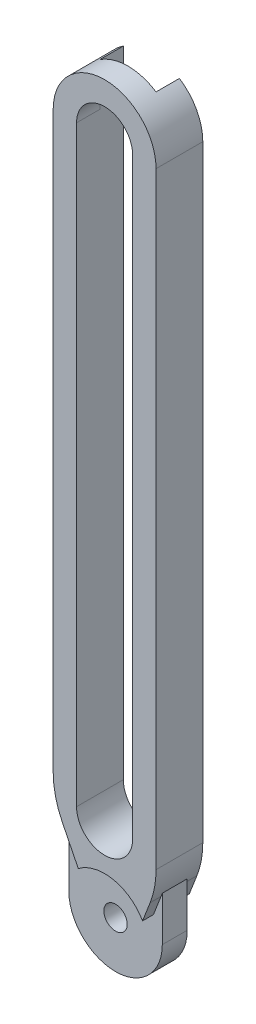
SolidWorks part; units mm, degrees
ref_plane "Piano frontale" through (0, 0, 0) normal (0, 0, 1) x (1, 0, 0)
ref_plane "Piano superiore" through (0, 0, 0) normal (0, 1, 0) x (1, 0, 0)
ref_plane "Piano destro" through (0, 0, 0) normal (1, 0, 0) x (0, 0, -1)
sketch "Schizzo1" plane through (0, 0, 0) normal (0, 0, 1) x (1, 0, 0)
  line L0 (0, -86.6264) -> (0, 113.3736) construction
  line L1 (-16.5, -86.6264) -> (-16.5, 113.3736)
  line L2 (16.5, -86.6264) -> (16.5, 113.3736)
  arc A0 (-16.5, -86.6264) -> (16.5, -86.6264) centre (0, -86.6264) ccw
  arc A1 (16.5, 113.3736) -> (-16.5, 113.3736) centre (0, 113.3736) ccw
  point P2 (0, 13.3736)
  dimension "D1" = 33
  dimension "D2" = 200
extrude "Estrusione-Estrusione1" add sketch "Schizzo1" along normal mid plane 15
sketch "Schizzo2" plane through (0, 0, 0) normal (0, 0, 1) x (1, 0, 0)
  line L0 (0, -88.7045) -> (0, -104.7045) construction
  line L1 (15, -88.7045) -> (15, -104.7045)
  line L2 (-15, -88.7045) -> (-15, -104.7045)
  line L3 (16.5, -86.6264) -> (-16.5, -86.6264) construction
  arc A0 (15, -88.7045) -> (-15, -88.7045) centre (0, -88.7045) ccw
  arc A1 (-15, -104.7045) -> (15, -104.7045) centre (0, -104.7045) ccw
  point P3 (0, -96.7045)
  dimension "D1" = 15
  dimension "D2" = 16
extrude "Estrusione-Estrusione2" add sketch "Schizzo2" along normal mid plane 8
sketch "Schizzo3" plane through (0, 0, 4) normal (0, 0, 1) x (1, 0, 0)
  line L0 (0, -104.7045) -> (15, -104.7045) construction
  line L1 (-8.4489, -93.5413) -> (-16.5, -77.3405)
  line L2 (-16.5, 113.3736) -> (-16.5, -86.6264) construction
  line L3 (-16.5, -77.3405) -> (-21.7067, -99.1177)
  line L4 (-21.7067, -99.1177) -> (-12.1597, -111.6429)
  line L5 (12.1644, -97.7744) -> (16.5, -86.6264)
  line L6 (16.5, -86.6264) -> (21.2626, -91.5332)
  line L7 (21.2626, -91.5332) -> (13.9976, -104.4458)
  arc A0 (-12.1597, -111.6429) -> (13.9976, -104.4458) centre (0, -104.7045) ccw
  arc A1 (12.1644, -97.7744) -> (-8.4489, -93.5413) centre (0, -104.7045) ccw
  arc A2 (-15, -93.5003) -> (15, -93.5003) centre (0, -86.6264) ccw construction
  dimension "D1" = 28
extrude "Taglio-Estrusione1" cut sketch "Schizzo3" along normal blind 4
mirror "Specchia1" about plane through (0, 0, 0) normal (0, 0, 1) of "Taglio-Estrusione1"
sketch "Schizzo4" plane through (0, 0, 4) normal (0, 0, 1) x (1, 0, 0)
  line L0 (-15, -93.5003) -> (-15, -80.3588)
  line L1 (-8.4489, -93.5413) -> (-16.5, -77.3405) construction
  line L2 (-15, -80.3588) -> (-16.5, -77.3405)
  line L3 (-16.5, -77.3405) -> (-16.5, -93.5003)
  line L4 (-16.5, -93.5003) -> (-15, -93.5003)
  line L5 (15, -93.5003) -> (15, -90.4833)
  line L6 (12.1644, -97.7744) -> (16.5, -86.6264) construction
  line L7 (15, -90.4833) -> (16.5, -86.6264)
  line L8 (16.5, -86.6264) -> (16.5, -93.5003)
  line L9 (16.5, -93.5003) -> (15, -93.5003)
extrude "Taglio-Estrusione2" cut sketch "Schizzo4" against normal blind 8
fillet "Raccordo1" radius 28 2 edges at (-16.5, -77.3405, 0) (16.5, -86.6264, 0)
sketch "Schizzo9" plane through (0, 0, 4) normal (0, 0, 1) x (1, 0, 0)
  line L0 (0, -104.7045) -> (15, -104.7045) construction
hole_wizard "Foro per Vite M6.5-1" positions "Schizzo3D4" profile "Schizzo10" hole size "M6.5" standard "ISO"
sketch3d "Schizzo3D4"
  point P0 (0, -104.7045, 4)
sketch "Schizzo10" plane through (0, -104.7045, 4) normal (1, 0, 0) x (0, -1, 0)
  line L0 (0, 0) -> (0, 10.2532)
  line L1 (0, 10.2532) -> (3.75, 8)
  line L2 (3.75, 8) -> (3.75, 0)
  line L5 (3.75, 0) -> (0, 0)
  line L10 (0, 10.2532) -> (-3.75, 8) construction
  line L11 (0, -6.35) -> (0, 107.95) construction
  dimension "Hole Dia." = 7.5
  dimension "Hole Depth" = 8
  dimension "Drill Angle" = 118
sketch "Schizzo11" plane through (0, 0, 7.5) normal (0, 0, 1) x (1, 0, 0)
  line L0 (0, 113.3736) -> (0, -76.6264) construction
  line L1 (9, 113.3736) -> (9, -76.6264)
  line L2 (-9, 113.3736) -> (-9, -76.6264)
  arc A0 (9, 113.3736) -> (-9, 113.3736) centre (0, 113.3736) ccw
  arc A1 (-9, -76.6264) -> (9, -76.6264) centre (0, -76.6264) ccw
  point P4 (0, 18.3736)
  dimension "D1" = 9
  dimension "D2" = 190
extrude "Taglio-Estrusione3" cut sketch "Schizzo11" against normal through all
sketch "Schizzo13" plane through (0, 0, -7.5) normal (0, 0, -1) x (-1, 0, 0)
  line L0 (0, 113.3736) -> (0, 158.8684) construction
  line L1 (-9, 113.3736) -> (-9, 158.8684)
  line L2 (9, 113.3736) -> (9, 158.8684)
  line L3 (-9, -76.6264) -> (-9, 113.3736) construction
  arc A0 (-9, 113.3736) -> (9, 113.3736) centre (0, 113.3736) ccw
  arc A1 (9, 158.8684) -> (-9, 158.8684) centre (0, 158.8684) ccw
  point P4 (0, 136.121)
extrude "Taglio-Estrusione4" cut sketch "Schizzo13" against normal blind 7.5
sketch "Schizzo14" plane through (0, 0, 4) normal (0, 0, 1) x (1, 0, 0)
equation "\"80ù\"=90"
